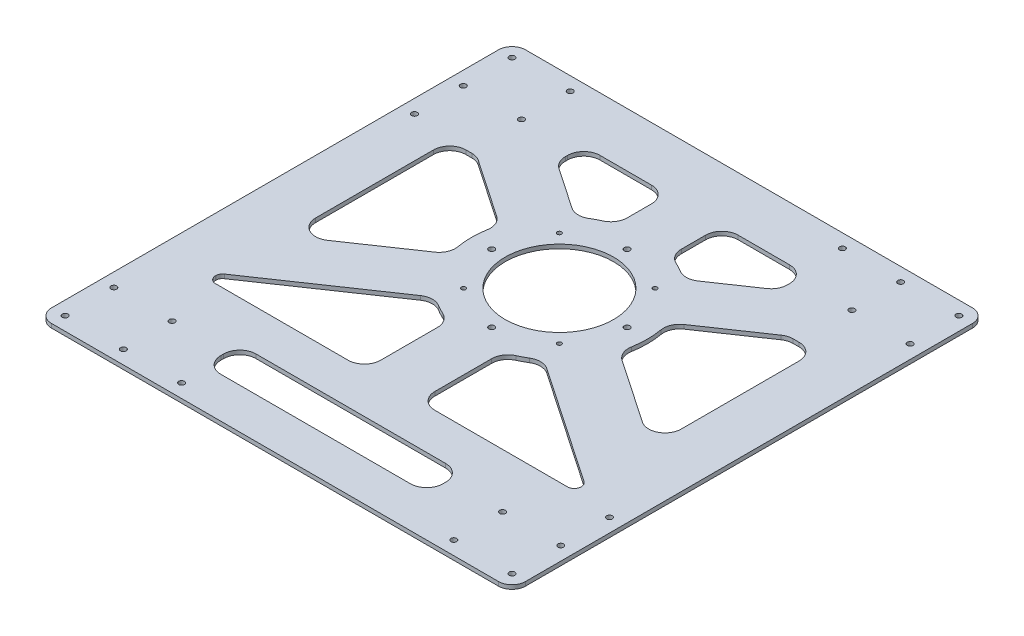
SolidWorks part; units mm, degrees
ref_plane "Front Plane" through (0, 0, 0) normal (0, 0, 1) x (1, 0, 0)
ref_plane "Top Plane" through (0, 0, 0) normal (0, 1, 0) x (1, 0, 0)
ref_plane "Right Plane" through (0, 0, 0) normal (1, 0, 0) x (0, 0, -1)
sketch "Sketch1" plane through (0, 0, 0) normal (0, 1, 0) x (1, 0, 0)
  line L1 (0, 0) -> (350, 0)
  line L2 (0, 0) -> (0, 350)
  line L3 (0, 350) -> (350, 350)
  line L4 (350, 0) -> (350, 350)
  dimension "D1" = 350
  dimension "D2" = 350
extrude "Boss-Extrude1" add sketch "Sketch1" along normal blind 3
fillet "Fillet1" radius 10 4 edges at (0, 1.5, -350) (350, 1.5, -350) (350, 1.5, 0) (0, 1.5, 0)
sketch "Sketch2" plane through (0, 3, 0) normal (0, 1, 0) x (1, 0, 0)
  line L0 (10, 340) -> (53, 340) construction
  line L1 (53, 340) -> (53, 304) construction
  line L2 (53, 304) -> (10, 304) construction
  line L3 (10, 304) -> (10, 340) construction
  line L4 (340, 350) -> (10, 350) construction
  line L5 (0, 340) -> (0, 10) construction
  line L6 (0, 175) -> (350, 175) construction
  line L7 (350, 10) -> (350, 340) construction
  line L8 (175, 350) -> (175, 0) construction
  line L9 (10, 0) -> (340, 0) construction
  circle A0 centre (10, 340) radius 2.1
  circle A1 centre (53, 340) radius 2.1
  circle A2 centre (53, 304) radius 2.1
  circle A3 centre (10, 304) radius 2.1
  circle A128 centre (10, 286) radius 2.1 [skipped]
  circle A129 centre (53, 286) radius 2.1 [skipped]
  circle A136 centre (254, 340) radius 2.1
  circle A137 centre (340, 82) radius 2.1
  circle A138 centre (297, 304) radius 2.1
  circle A139 centre (340, 304) radius 2.1
  circle A140 centre (297, 340) radius 2.1
  circle A141 centre (340, 340) radius 2.1
  circle A142 centre (340, 10) radius 2.1
  circle A143 centre (340, 46) radius 2.1
  circle A144 centre (297, 10) radius 2.1
  circle A145 centre (297, 46) radius 2.1
  circle A146 centre (53, 10) radius 2.1
  circle A147 centre (53, 46) radius 2.1
  circle A148 centre (10, 46) radius 2.1
  circle A149 centre (10, 10) radius 2.1
  circle A150 centre (53, 322) radius 2.1 [skipped]
  circle A151 centre (10, 322) radius 2.1 [skipped]
  circle A152 centre (96, 10) radius 2.1
  circle A153 centre (10, 268) radius 2.1
  dimension "D1" = 4.2
  dimension "D2" = 10
  dimension "D3" = 10
  dimension "D4" = 43
  dimension "D5" = 36
  dimension "D7" = 43
  dimension "D9" = 43
  dimension "D8" = 36
  dimension "D10" = 36
  dimension "D6" = 2
extrude "Cut-Extrude1" cut sketch "Sketch2" against normal through all
sketch "Sketch3" plane through (0, 3, 0) normal (0, 1, 0) x (1, 0, 0)
  line L0 (175, 350) -> (175, 0) construction
  line L9 (340, 350) -> (10, 350) construction
  line L10 (10, 0) -> (340, 0) construction
  line L11 (0, 175) -> (350, 175) construction
  line L12 (0, 340) -> (0, 10) construction
  line L13 (350, 10) -> (350, 340) construction
  line L14 (93, 290) -> (310, 142.3142)
  line L15 (40, 264) -> (310, 264)
  line L16 (40, 264) -> (40, 86)
  line L17 (40, 86) -> (310, 86)
  line L18 (310, 264) -> (310, 86)
  line L19 (93, 310) -> (257, 310)
  line L20 (93, 310) -> (93, 40)
  line L21 (93, 40) -> (257, 40)
  line L22 (257, 310) -> (257, 40)
  line L27 (60.109, 264) -> (310, 93.9293)
  line L28 (257, 290) -> (40, 142.3142)
  line L29 (289.891, 264) -> (40, 93.9293)
  line L30 (139.4531, 210) -> (210.5469, 210) construction
  line L32 (155, 310) -> (195, 310)
  line L33 (155, 310) -> (155, 40)
  line L34 (155, 40) -> (195, 40)
  line L35 (195, 310) -> (195, 40)
  line L36 (93, 40) -> (257, 40)
  line L37 (93, 40) -> (93, 30)
  line L38 (93, 30) -> (257, 30)
  line L39 (257, 40) -> (257, 30)
  circle A2 centre (175, 210) radius 40
  circle A3 centre (175, 210) radius 65
  circle A6 centre (297, 340) radius 2.1 construction
  circle A7 centre (297, 304) radius 2.1 construction
  point P4 (40, 175)
  point P5 (175, 264)
  point P22 (93, 175)
  point P27 (175, 310)
  point P31 (175, 310)
  dimension "D5" = 80
  dimension "D6" = 130
  dimension "D1" = 40
  dimension "D2" = 40
  dimension "D3" = 40
  dimension "D4" = 40
  dimension "D7" = 100
  dimension "D8" = 40
  dimension "D9" = 20
  dimension "D10" = 40
  dimension "D11" = 10
extrude "Cut-Extrude2" cut sketch "Sketch3" against normal blind 10 contours A3 L33 L19 L20 L14 L15 | A3 L15 L28 L22 L19 L35 | A3 L15 L14 | A3 L28 L15 | L28 L20 L27 L15 L16 | A3 L27 L20 L28 | A3 L14 L22 L29 | L15 L29 L22 L14 L18 | L27 L22 L17 L18 | A3 L35 L17 L22 L27 | L20 L29 L16 L17 | A3 L29 L20 L17 L33 | L35 A2 L28 L14 | L14 A2 L35 | L28 A2 L14 | L33 A2 L28 | L14 A2 L33 L28 | L35 L14 L28 L33 L27 L29 | L28 A2 L27 L33 | L27 A2 L33 | L33 A2 L29 L27 | L29 A2 L27 | L27 A2 L35 L29 | L35 A2 L29 | L29 A2 L14 L35 | L17 L35 L21 L22 | L33 L17 L20 L21 | L35 L17 L33 L21 | L39 L21 L37 L38 | L14 A2 L29 | L27 A2 L28 region at (127.1846, 3, -290.7445) region at (135.0257, 3, -263.1157) region at (63.7367, 3, -208.4277) region at (101.2594, 3, -210) region at (222.8154, 3, -290.7445) region at (175, 3, -243.8071) region at (161.755, 3, -234.0102) region at (146.352, 3, -225.8276) region at (136.5088, 3, -210) region at (125.9526, 3, -117.033) region at (72.6357, 3, -101.0703) region at (188.245, 3, -234.0102) region at (175, 3, -210) region at (149.8177, 3, -210) region at (146.352, 3, -194.1724) region at (214.9743, 3, -263.1157) region at (124, 3, -63) region at (203.648, 3, -225.8276) region at (200.1823, 3, -210) region at (161.755, 3, -185.9898) region at (175, 3, -63) region at (175, 3, -35) region at (213.4912, 3, -210) region at (203.648, 3, -194.1724) region at (188.245, 3, -185.9898) region at (175, 3, -176.1929) region at (224.0474, 3, -117.033) region at (248.7406, 3, -210) region at (286.2633, 3, -208.4277) region at (226, 3, -63) region at (277.3643, 3, -101.0703)
sketch "Sketch6" plane through (0, 3, 0) normal (0, 1, 0) x (1, 0, 0)
  line L0 (257, 86) -> (257, 30) construction
  line L1 (93, 86) -> (257, 86)
  line L2 (93, 86) -> (93, 56)
  line L3 (93, 56) -> (257, 56)
  line L4 (257, 86) -> (257, 56)
  line L5 (257, 86) -> (310, 86) construction
  dimension "D1" = 30
extrude "Boss-Extrude2" add sketch "Sketch6" against normal up to surface (3 mm away) up to face at (175, 0, -250)
fillet "Fillet2" radius 12 30 edges at (135.124, 1.5, -158.6687) (155, 1.5, -148.1534) (214.876, 1.5, -158.6687) (195, 1.5, -148.1534) (289.891, 1.5, -264) (310, 1.5, -264) (310, 1.5, -142.3142) (237.3815, 1.5, -228.2631) (237.3815, 1.5, -191.7369) (195, 1.5, -271.8466) (214.876, 1.5, -261.3313) (257, 1.5, -290) (257, 1.5, -310) (155, 1.5, -310) (135.124, 1.5, -261.3313) (155, 1.5, -271.8466) (93, 1.5, -290) (195, 1.5, -310) (93, 1.5, -310) (40, 1.5, -142.3142) (112.6185, 1.5, -191.7369) (112.6185, 1.5, -228.2631) (60.109, 1.5, -264) (40, 1.5, -264) (195, 1.5, -86) (155, 1.5, -86) (93, 1.5, -56) (257, 1.5, -56) (257, 1.5, -30) (93, 1.5, -30)
fillet "Fillet3" radius 5 4 edges at (310, 1.5, -86) (310, 1.5, -93.9293) (40, 1.5, -86) (40, 1.5, -93.9293)
sketch "Sketch5" plane through (0, 3, 0) normal (0, 1, 0) x (1, 0, 0)
  line L0 (175, 260) -> (175, 210) construction
  line L2 (210.3553, 245.3553) -> (175, 210) construction
  circle A0 centre (175, 210) radius 50 construction
  circle A1 centre (175, 260) radius 2.1
  circle A2 centre (225, 210) radius 2.1
  circle A3 centre (175, 160) radius 2.1
  circle A4 centre (125, 210) radius 2.1
  circle A9 centre (210.3553, 245.3553) radius 1.6
  circle A10 centre (210.3553, 174.6447) radius 1.6
  circle A11 centre (139.6447, 174.6447) radius 1.6
  circle A12 centre (139.6447, 245.3553) radius 1.6
  point P22 (175, 210)
  point P39 (175, 210)
  dimension "D1" = 100
  dimension "D2" = 4.2
  dimension "D4" = 4
  dimension "3.2" = 3.2
  dimension "D5" = 45
  dimension "D3" = 4
extrude "Cut-Extrude4" cut sketch "Sketch5" against normal blind 10
